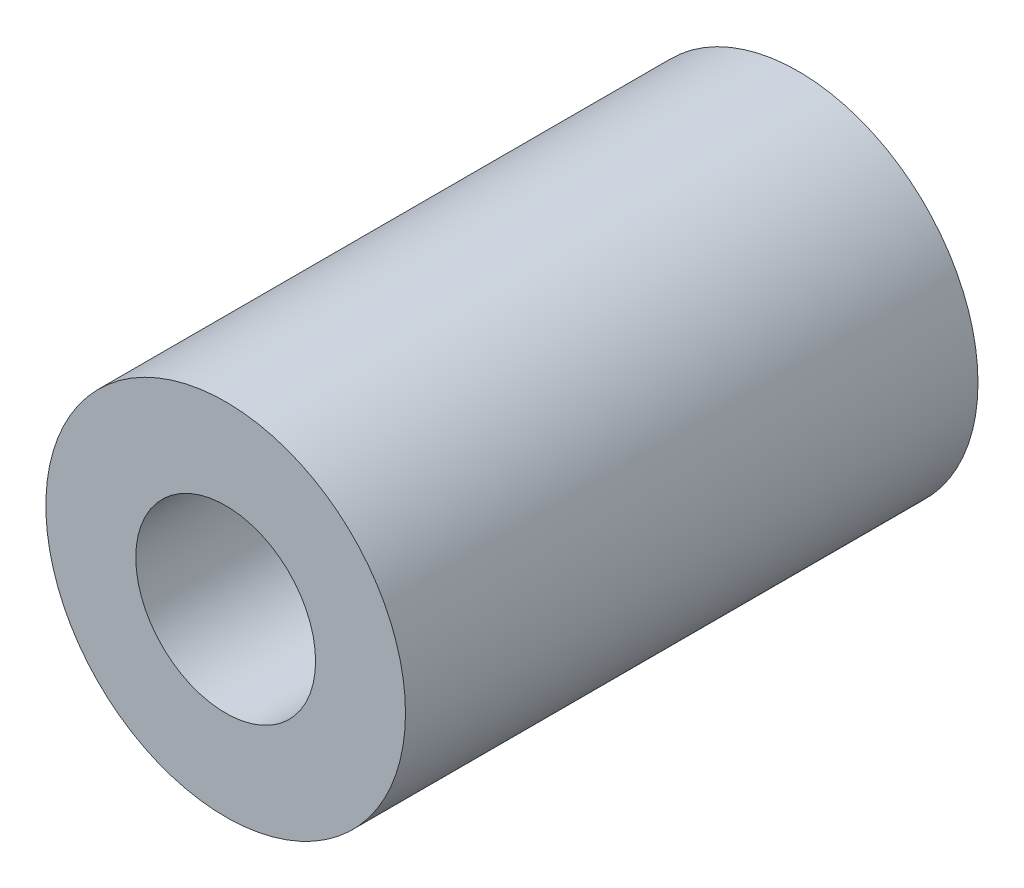
SolidWorks part; units mm, degrees
material "ABS"
ref_plane "Front Plane" through (0, 0, 0) normal (0, 0, 1) x (1, 0, 0)
ref_plane "Top Plane" through (0, 0, 0) normal (0, 1, 0) x (1, 0, 0)
ref_plane "Right Plane" through (0, 0, 0) normal (1, 0, 0) x (0, 0, -1)
sketch "Sketch1" plane through (0, 0, 0) normal (0, 0, 1) x (1, 0, 0)
  circle A0 centre (0, 0) radius 1.5875
  circle A1 centre (0, 0) radius 3.175
  dimension "D1" = 3.175
  dimension "D2" = 6.35
extrude "Boss-Extrude1" add sketch "Sketch1" along normal blind 10.1092
